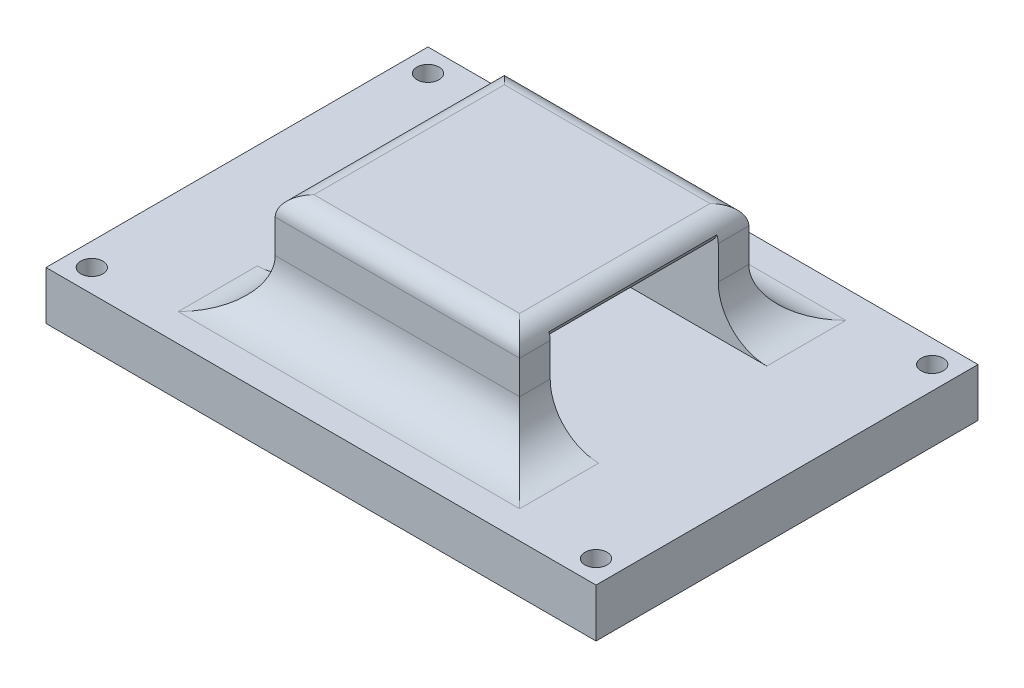
SolidWorks part; units mm, degrees
material "ABS"
ref_plane "Front Plane" through (0, 0, 0) normal (0, 0, 1) x (1, 0, 0)
ref_plane "Top Plane" through (0, 0, 0) normal (0, 1, 0) x (1, 0, 0)
ref_plane "Right Plane" through (0, 0, 0) normal (1, 0, 0) x (0, 0, -1)
sketch "Sketch2" plane through (0, 0, 0) normal (1, 0, 0) x (0, 0, -1)
  line L0 (0, -11.35) -> (0, 0) construction
  line L1 (-11, -5) -> (11, -5)
  line L2 (-11, -5) -> (-11, 5)
  line L3 (-11, 5) -> (11, 5)
  line L4 (11, -5) -> (11, 5)
  line L5 (-11, -5) -> (11, 5) construction
  line L6 (-11, 5) -> (11, -5) construction
  line L7 (-15, -11.35) -> (15, -11.35)
  line L8 (-15, -11.35) -> (-15, 8.25)
  line L9 (-15, 8.25) -> (15, 8.25)
  line L10 (15, -11.35) -> (15, 8.25)
  point P0 (0, 0)
  point P5 (0, 0)
  dimension "D1" = 22
  dimension "D2" = 30
  dimension "D3" = 3.25
  dimension "D4" = 10
  dimension "D5" = 6.35
extrude "Boss-Extrude2" add sketch "Sketch2" along normal blind 32
sketch "Sketch3" plane through (0, -11.35, 0) normal (0, -1, 0) x (1, 0, 0)
  line L0 (32, 15) -> (0, 15) construction
  line L1 (-20, -25) -> (52, -25)
  line L2 (-20, -25) -> (-20, 25)
  line L3 (-20, 25) -> (52, 25)
  line L4 (52, -25) -> (52, 25)
  line L5 (32, -15) -> (0, -15) construction
  line L6 (0, 15) -> (0, -15) construction
  line L7 (32, 15) -> (32, -15) construction
  dimension "D1" = 10
  dimension "D2" = 10
  dimension "D3" = 20
  dimension "D4" = 20
extrude "Boss-Extrude3" add sketch "Sketch3" against normal up to surface (6.35 mm away) up to face at (16, -5, 0)
sketch "Sketch4" plane through (0, -5, 0) normal (0, 1, 0) x (1, 0, 0)
  line L1 (52, -25) -> (-20, -25) construction
  line L2 (-20, -25) -> (-20, 25) construction
  circle A0 centre (-17, -22) radius 1.45
  dimension "D1" = 2.9
  dimension "D2" = 3
  dimension "D3" = 3
extrude "Cut-Extrude1" cut sketch "Sketch4" against normal up to surface (6.35 mm away) up to face at (16, -11.35, 0)
pattern_linear "LPattern1" count 2 spacing 66 along (1, 0, 0) count 2 spacing 44 along (0, 0, -1) of "Cut-Extrude1"
fillet "Fillet1" radius 6.35 6 edges at (32, -5, -13) (32, -5, 13) (0, -5, 13) (0, -5, -13) (16, -5, -15) (16, -5, 15)
fillet "Fillet2" radius 2.54 4 edges at (32, 8.25, 0) (16, 8.25, -15) (0, 8.25, 0) (16, 8.25, 15)
fillet "Fillet3" radius 2.54 2 edges at (0, 5, 0) (32, 5, 0)
